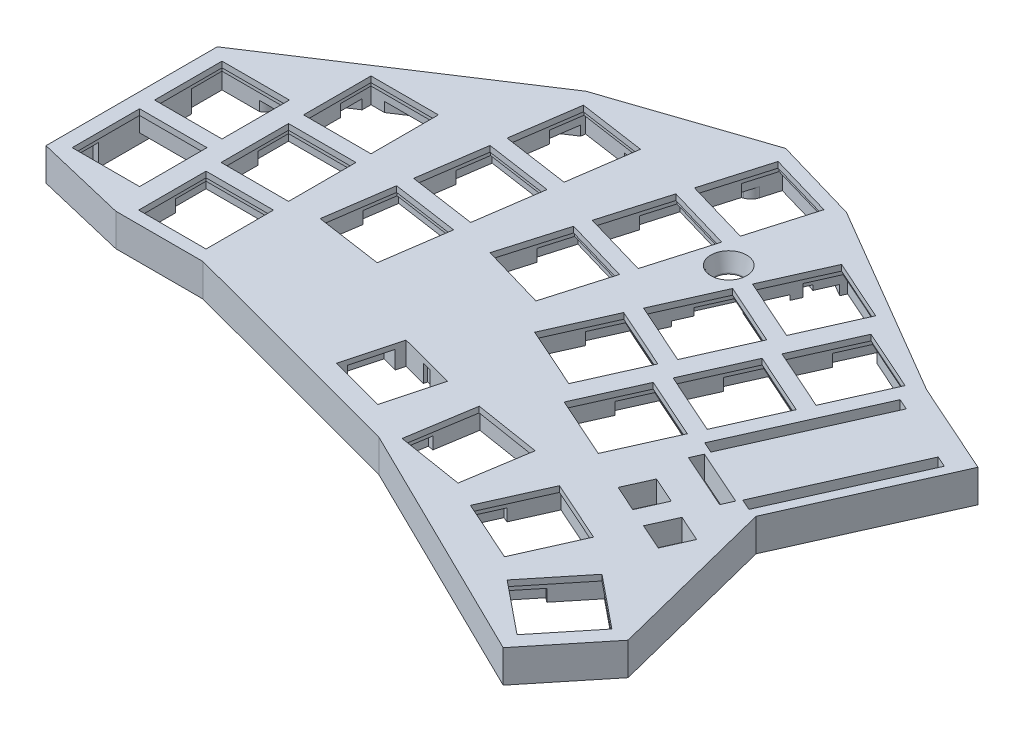
SolidWorks part; units mm, degrees
ref_plane "Front Plane" through (0, 0, 0) normal (0, 0, 1) x (1, 0, 0)
ref_plane "Top Plane" through (0, 0, 0) normal (0, 1, 0) x (1, 0, 0)
ref_plane "Right Plane" through (0, 0, 0) normal (1, 0, 0) x (0, 0, -1)
sketch "Ergogen Drawing" plane through (0, 0, 0) normal (0, 1, 0) x (1, 0, 0)
  line L0 (0.027, 17.9992) -> (18.027, 17.9992)
  line L1 (18.027, 17.9992) -> (18.027, -0.0008)
  line L2 (18.027, -0.0008) -> (0.027, -0.0008)
  line L3 (0.027, -0.0008) -> (0.027, 17.9992)
  line L4 (0.027, 34.9992) -> (18.027, 34.9992)
  line L5 (18.027, 34.9992) -> (18.027, 16.9992)
  line L6 (18.027, 16.9992) -> (0.027, 16.9992)
  line L7 (0.027, 16.9992) -> (0.027, 34.9992)
  line L8 (18.027, 15.9992) -> (36.027, 15.9992)
  line L9 (36.027, 15.9992) -> (36.027, -2.0008)
  line L10 (36.027, -2.0008) -> (18.027, -2.0008)
  line L11 (18.027, -2.0008) -> (18.027, 15.9992)
  line L12 (18.027, 32.9992) -> (36.027, 32.9992)
  line L13 (36.027, 32.9992) -> (36.027, 14.9992)
  line L14 (36.027, 14.9992) -> (18.027, 14.9992)
  line L15 (18.027, 14.9992) -> (18.027, 32.9992)
  line L16 (18.027, 49.9992) -> (36.027, 49.9992)
  line L17 (36.027, 49.9992) -> (36.027, 31.9992)
  line L18 (36.027, 31.9992) -> (18.027, 31.9992)
  line L19 (18.027, 31.9992) -> (18.027, 49.9992)
  line L20 (41.3768, 32.6051) -> (59.3329, 31.3495)
  line L21 (59.3329, 31.3495) -> (58.0773, 13.3933)
  line L22 (58.0773, 13.3933) -> (40.1211, 14.6489)
  line L23 (40.1211, 14.6489) -> (41.3768, 32.6051)
  line L24 (42.5626, 49.5637) -> (60.5188, 48.3081)
  line L25 (60.5188, 48.3081) -> (59.2631, 30.3519)
  line L26 (59.2631, 30.3519) -> (41.307, 31.6075)
  line L27 (41.307, 31.6075) -> (42.5626, 49.5637)
  line L28 (43.7485, 66.5223) -> (61.7046, 65.2667)
  line L29 (61.7046, 65.2667) -> (60.449, 47.3105)
  line L30 (60.449, 47.3105) -> (42.4929, 48.5661)
  line L31 (42.4929, 48.5661) -> (43.7485, 66.5223)
  line L32 (66.0898, 43.7082) -> (83.8507, 40.7838)
  line L33 (83.8507, 40.7838) -> (80.9263, 23.023)
  line L34 (80.9263, 23.023) -> (63.1655, 25.9473)
  line L35 (63.1655, 25.9473) -> (66.0898, 43.7082)
  line L36 (68.8517, 60.4823) -> (86.6126, 57.558)
  line L37 (86.6126, 57.558) -> (83.6882, 39.7971)
  line L38 (83.6882, 39.7971) -> (65.9274, 42.7215)
  line L39 (65.9274, 42.7215) -> (68.8517, 60.4823)
  line L40 (71.6136, 77.2565) -> (89.3745, 74.3321)
  line L41 (89.3745, 74.3321) -> (86.4501, 56.5713)
  line L42 (86.4501, 56.5713) -> (68.6893, 59.4956)
  line L43 (68.6893, 59.4956) -> (71.6136, 77.2565)
  line L44 (88.5581, 32.769) -> (105.9366, 28.0799)
  line L45 (105.9366, 28.0799) -> (101.2475, 10.7014)
  line L46 (101.2475, 10.7014) -> (83.869, 15.3905)
  line L47 (83.869, 15.3905) -> (88.5581, 32.769)
  line L48 (92.9866, 49.182) -> (110.3652, 44.4929)
  line L49 (110.3652, 44.4929) -> (105.6761, 27.1144)
  line L50 (105.6761, 27.1144) -> (88.2976, 31.8035)
  line L51 (88.2976, 31.8035) -> (92.9866, 49.182)
  line L52 (97.4152, 65.595) -> (114.7937, 60.906)
  line L53 (114.7937, 60.906) -> (110.1046, 43.5274)
  line L54 (110.1046, 43.5274) -> (92.7261, 48.2165)
  line L55 (92.7261, 48.2165) -> (97.4152, 65.595)
  line L56 (107.0448, 26.9674) -> (124.0477, 21.0597)
  line L57 (124.0477, 21.0597) -> (118.14, 4.0568)
  line L58 (118.14, 4.0568) -> (101.1371, 9.9645)
  line L59 (101.1371, 9.9645) -> (107.0448, 26.9674)
  line L60 (112.6243, 43.0257) -> (129.6273, 37.118)
  line L61 (129.6273, 37.118) -> (123.7195, 20.1151)
  line L62 (123.7195, 20.1151) -> (106.7166, 26.0228)
  line L63 (106.7166, 26.0228) -> (112.6243, 43.0257)
  line L64 (118.2039, 59.084) -> (135.2068, 53.1763)
  line L65 (135.2068, 53.1763) -> (129.299, 36.1734)
  line L66 (129.299, 36.1734) -> (112.2961, 42.0811)
  line L67 (112.2961, 42.0811) -> (118.2039, 59.084)
  line L68 (95.4197, 6.4051) -> (112.5714, 0.9445)
  line L69 (112.5714, 0.9445) -> (107.1108, -16.2072)
  line L70 (107.1108, -16.2072) -> (89.959, -10.7466)
  line L71 (89.959, -10.7466) -> (95.4197, 6.4051)
  line L72 (116.0129, -0.5249) -> (131.9353, -8.9198)
  line L73 (131.9353, -8.9198) -> (123.5404, -24.8423)
  line L74 (123.5404, -24.8423) -> (107.6179, -16.4473)
  line L75 (107.6179, -16.4473) -> (116.0129, -0.5249)
  line L76 (135.0644, -10.9721) -> (149.2602, -22.0392)
  line L77 (149.2602, -22.0392) -> (138.1931, -36.235)
  line L78 (138.1931, -36.235) -> (123.9973, -25.1679)
  line L79 (123.9973, -25.1679) -> (135.0644, -10.9721)
sketch "Layout Based on OG" plane through (0, 0, 0) normal (0, 1, 0) x (1, 0, 0)
  line L0 (0, 0) -> (0, 17) construction
  line L1 (0, 17) -> (18, 17) construction
  line L2 (18, 17) -> (18, 0) construction
  line L3 (18, 0) -> (0, 0) construction
  line L4 (2.05, 1.55) -> (2.05, 15.45)
  line L5 (2.05, 15.45) -> (15.95, 15.45)
  line L6 (15.95, 15.45) -> (15.95, 1.55)
  line L7 (15.95, 1.55) -> (2.05, 1.55)
  line L8 (109.1798, 58.6066) -> (27, -125.5436) construction
  line L9 (27, 46.7087) -> (27, -125.5436) construction
  line L10 (84.3863, 71.4039) -> (27, -125.5436) construction
  line L11 (54.2678, 62.3831) -> (27, -125.5436) construction
  line L12 (44.7261, 45.0233) -> (58.4821, 43.0274)
  line L13 (2.05, 18.55) -> (15.95, 18.55)
  line L14 (2.05, 18.55) -> (2.05, 32.45)
  line L15 (2.05, 32.45) -> (15.95, 32.45)
  line L16 (15.95, 18.55) -> (15.95, 32.45)
  line L17 (20.05, 31.2587) -> (33.95, 31.2587)
  line L18 (20.05, 31.2587) -> (20.05, 45.1587)
  line L19 (20.05, 45.1587) -> (33.95, 45.1587)
  line L20 (33.95, 31.2587) -> (33.95, 45.1587)
  line L21 (33.95, 28.1587) -> (20.05, 28.1587)
  line L22 (33.95, 28.1587) -> (33.95, 14.2587)
  line L23 (33.95, 14.2587) -> (20.05, 14.2587)
  line L24 (20.05, 28.1587) -> (20.05, 14.2587)
  line L25 (20.05, -2.7413) -> (33.95, -2.7413)
  line L26 (20.05, -2.7413) -> (20.05, 11.1587)
  line L27 (20.05, 11.1587) -> (33.95, 11.1587)
  line L28 (33.95, -2.7413) -> (33.95, 11.1587)
  line L29 (44.7261, 45.0233) -> (42.7302, 31.2674)
  line L30 (58.4821, 43.0274) -> (56.4861, 29.2714)
  line L31 (42.7302, 31.2674) -> (56.4861, 29.2714)
  line L32 (42.285, 28.1995) -> (56.041, 26.2036)
  line L33 (42.285, 28.1995) -> (40.2891, 14.4436)
  line L34 (56.041, 26.2036) -> (54.045, 12.4476)
  line L35 (40.2891, 14.4436) -> (54.045, 12.4476)
  line L36 (47.1672, 61.8472) -> (60.9232, 59.8512)
  line L37 (47.1672, 61.8472) -> (45.1712, 48.0912)
  line L38 (60.9232, 59.8512) -> (58.9272, 46.0953)
  line L39 (45.1712, 48.0912) -> (58.9272, 46.0953)
  line L40 (77.2802, 71.86) -> (90.6252, 67.9716)
  line L41 (77.2802, 71.86) -> (73.3917, 58.515)
  line L42 (90.6252, 67.9716) -> (86.7368, 54.6265)
  line L43 (73.3917, 58.515) -> (86.7368, 54.6265)
  line L44 (85.8695, 51.6503) -> (72.5245, 55.5388)
  line L45 (85.8695, 51.6503) -> (81.9811, 38.3053)
  line L46 (72.5245, 55.5388) -> (68.6361, 42.1937)
  line L47 (81.9811, 38.3053) -> (68.6361, 42.1937)
  line L48 (67.7688, 39.2175) -> (81.1139, 35.329)
  line L49 (67.7688, 39.2175) -> (63.8804, 25.8725)
  line L50 (81.1139, 35.329) -> (77.2254, 21.984)
  line L51 (63.8804, 25.8725) -> (77.2254, 21.984)
  line L52 (102.2015, 60.0235) -> (114.8949, 54.3589)
  line L53 (102.2015, 60.0235) -> (96.5369, 47.3301)
  line L54 (114.8949, 54.3589) -> (109.2302, 41.6655)
  line L55 (96.5369, 47.3301) -> (109.2302, 41.6655)
  line L56 (107.9669, 38.8346) -> (95.2735, 44.4992)
  line L57 (107.9669, 38.8346) -> (102.3023, 26.1412)
  line L58 (95.2735, 44.4992) -> (89.6089, 31.8058)
  line L59 (102.3023, 26.1412) -> (89.6089, 31.8058)
  line L60 (101.039, 23.3103) -> (88.3456, 28.9749)
  line L61 (101.039, 23.3103) -> (95.3744, 10.6169)
  line L62 (88.3456, 28.9749) -> (82.681, 16.2815)
  line L63 (95.3744, 10.6169) -> (82.681, 16.2815)
  line L64 (117.7053, 50.5958) -> (130.3987, 44.9312)
  line L65 (117.7053, 50.5958) -> (112.0407, 37.9024)
  line L66 (130.3987, 44.9312) -> (124.734, 32.2378)
  line L67 (112.0407, 37.9024) -> (124.734, 32.2378)
  line L68 (123.4707, 29.4069) -> (110.7773, 35.0715)
  line L69 (123.4707, 29.4069) -> (117.8061, 16.7135)
  line L70 (110.7773, 35.0715) -> (105.1127, 22.3782)
  line L71 (117.8061, 16.7135) -> (105.1127, 22.3782)
  line L72 (116.5428, 13.8826) -> (103.8494, 19.5473)
  line L73 (116.5428, 13.8826) -> (110.8782, 1.1892)
  line L74 (103.8494, 19.5473) -> (98.1848, 6.8539)
  line L75 (110.8782, 1.1892) -> (98.1848, 6.8539)
  line L76 (90.1692, -2.6429) -> (103.8962, -4.8292)
  line L77 (90.1692, -2.6429) -> (87.9829, -16.3699)
  line L78 (103.8962, -4.8292) -> (101.7099, -18.5562)
  line L79 (87.9829, -16.3699) -> (101.7099, -18.5562)
  line L80 (112.6329, -8.5638) -> (125.3263, -14.2284)
  line L81 (112.6329, -8.5638) -> (106.9683, -21.2572)
  line L82 (125.3263, -14.2284) -> (119.6617, -26.9218)
  line L83 (106.9683, -21.2572) -> (119.6617, -26.9218)
  line L84 (132.8305, -19.9983) -> (143.6253, -28.7552)
  line L85 (132.8305, -19.9983) -> (124.0737, -30.7931)
  line L86 (143.6253, -28.7552) -> (134.8684, -39.55)
  line L87 (124.0737, -30.7931) -> (134.8684, -39.55)
  line L88 (0, 0) -> (0, 34) construction
  line L89 (0, 34) -> (18, 46.7087) construction
  line L90 (18, 46.7087) -> (45.361, 63.6755) construction
  line L91 (45.361, 63.6755) -> (75.7456, 73.9216) construction
  line L92 (75.7456, 73.9216) -> (93.027, 68.8862) construction
  line L93 (93.027, 68.8862) -> (117.3986, 54.9389) construction
  line L94 (117.3986, 54.9389) -> (132.9024, 45.5112) construction
  line L95 (146.1938, -28.843) -> (135.484, -42.0452) construction
  line L96 (135.484, -42.0452) -> (85.7146, -17.5782) construction
  line L97 (0, 0) -> (18, -4.2913) construction
  line L98 (132.9024, 45.5112) -> (119.0465, 14.4627) construction
  line L99 (18, -4.2913) -> (36, -4.2913) construction
  line L100 (36, -4.2913) -> (85.7146, -17.5782) construction
  line L101 (119.0465, 14.4627) -> (137.3104, 6.3121) construction
  line L102 (137.3104, 6.3121) -> (151.1662, 37.3607) construction
  line L103 (151.1662, 37.3607) -> (132.9024, 45.5112) construction
  line L104 (146.1938, -28.843) -> (137.3104, 6.3121) construction
  line L105 (137.3104, 6.3121) -> (151.1662, 37.3607) construction
  line L106 (151.1662, 37.3607) -> (132.9024, 45.5112) construction
  line L107 (119.9597, 14.0551) -> (132.3892, 41.9075)
  line L108 (132.3892, 41.9075) -> (134.6722, 40.8887)
  line L109 (134.6722, 40.8887) -> (122.2427, 13.0363)
  line L110 (122.2427, 13.0363) -> (119.9597, 14.0551)
  line L111 (136.3972, 6.7197) -> (148.8267, 34.5721)
  line L112 (148.8267, 34.5721) -> (146.5437, 35.5909)
  line L113 (146.5437, 35.5909) -> (134.1142, 7.7385)
  line L114 (134.1142, 7.7385) -> (136.3972, 6.7197)
  line L115 (79.4058, -12.7868) -> (67.8127, -9.6883)
  line L116 (67.8127, -9.6883) -> (70.8336, 1.6149)
  line L117 (70.8336, 1.6149) -> (82.4267, -1.4835)
  line L118 (82.4267, -1.4835) -> (79.4058, -12.7868)
  line L119 (97.0327, -3.7361) -> (94.8464, -17.4631) construction
  line L120 (118.9913, -2.8379) -> (121.4364, 2.6412)
  line L121 (121.4364, 2.6412) -> (126.9156, 0.1961)
  line L122 (76.6302, 0.0657) -> (73.6092, -11.2375) construction
  line L123 (126.9156, 0.1961) -> (124.4704, -5.2831)
  line L124 (124.4704, -5.2831) -> (118.9913, -2.8379)
  line L125 (128.4611, -7.064) -> (130.9062, -1.5848)
  line L126 (130.9062, -1.5848) -> (136.3854, -4.03)
  line L127 (136.3854, -4.03) -> (133.9402, -9.5091)
  line L128 (133.9402, -9.5091) -> (128.4611, -7.064)
  line L137 (124.176, 1.4187) -> (121.7308, -4.0605) construction
  line L138 (133.6458, -2.8074) -> (131.2006, -8.2865) construction
  line L139 (126.7317, 7.1456) -> (128.1784, 10.3874) construction
  line L140 (135.0103, 42.8732) -> (147.795, 37.1678) construction
  line L141 (147.795, 37.1678) -> (133.1241, 4.2929) construction
  line L142 (133.1241, 4.2929) -> (120.3393, 9.9982) construction
  line L143 (120.3393, 9.9982) -> (135.0103, 42.8732) construction
  line L144 (120.9329, 9.7333) -> (121.9517, 12.0163)
  line L145 (121.9517, 12.0163) -> (133.5493, 6.8407)
  line L146 (133.5493, 6.8407) -> (132.5305, 4.5578)
  line L147 (132.5305, 4.5578) -> (120.9329, 9.7333)
  line L148 (126.9156, 0.1961) -> (140.3735, -5.8097) construction
  line L164 (-1, 34.5181) -> (-1, -0.7896)
  line L165 (-1, -0.7896) -> (17.8824, -5.2913)
  line L166 (17.8824, -5.2913) -> (35.8687, -5.2913)
  line L167 (35.8687, -5.2913) -> (85.3615, -18.5189)
  line L168 (85.3615, -18.5189) -> (135.7583, -43.2944)
  line L169 (135.7583, -43.2944) -> (147.2861, -29.0838)
  line L170 (147.2861, -29.0838) -> (138.3648, 6.2211)
  line L171 (138.3648, 6.2211) -> (152.487, 37.8664)
  line L172 (152.487, 37.8664) -> (133.3678, 46.3986)
  line L173 (133.3678, 46.3986) -> (117.9068, 55.8002) construction
  line L174 (117.9068, 55.8002) -> (93.4207, 69.8131) construction
  line L175 (93.4207, 69.8131) -> (75.7238, 74.9696)
  line L176 (75.7238, 74.9696) -> (44.9321, 64.5862)
  line L177 (44.9321, 64.5862) -> (17.4476, 47.5429) construction
  line L178 (17.4476, 47.5429) -> (-1, 34.5181) construction
  line L179 (-1, 34.5181) -> (44.9321, 64.5862)
  line L180 (133.3678, 46.3986) -> (93.4207, 69.8131)
  line L181 (27, -125.5436) -> (90.7493, 48.2155) construction
  circle A0 centre (142.6577, -23.0128) radius 2 construction
  circle A1 centre (142.6577, -23.0128) radius 1
  circle A2 centre (99.1237, -21.9416) radius 2 construction
  circle A3 centre (99.1237, -21.9416) radius 1
  circle A6 centre (16.2, -1.8061) radius 2 construction
  circle A7 centre (16.2, -1.8061) radius 1
  circle A8 centre (7.0467, 36.2) radius 2 construction
  circle A9 centre (7.0467, 36.2) radius 1
  circle A10 centre (72.7535, 70.802) radius 2 construction
  circle A11 centre (72.7535, 70.802) radius 1
  circle A12 centre (144.6437, 38.0814) radius 2 construction
  circle A13 centre (144.6437, 38.0814) radius 1
  circle A14 centre (90.7493, 48.2155) radius 3
  point P10 (110.8277, 18.1304)
  point P11 (117.7557, 33.6547)
  point P128 (75.1197, -5.5859)
  point P129 (95.9395, -10.5996)
  point P146 (127.7505, 9.4285)
  point P148 (128.1784, 10.3874)
  point P150 (122.9534, -1.3209)
  line B0 (18, 29.7087) -> (18, 46.7087) construction
  line B1 (18, 46.7087) -> (36, 46.7087) construction
  line B2 (36, 46.7087) -> (36, 29.7087) construction
  line B3 (36, 29.7087) -> (18, 29.7087) construction
  line B4 (20.05, 31.2587) -> (20.05, 45.1587) construction
  line B5 (20.05, 45.1587) -> (33.95, 45.1587) construction
  line B6 (33.95, 45.1587) -> (33.95, 31.2587) construction
  line B7 (33.95, 31.2587) -> (20.05, 31.2587) construction
  line B8 (18, 12.7087) -> (18, 29.7087) construction
  line B9 (18, 29.7087) -> (36, 29.7087) construction
  line B10 (36, 29.7087) -> (36, 12.7087) construction
  line B11 (36, 12.7087) -> (18, 12.7087) construction
  line B12 (20.05, 14.2587) -> (20.05, 28.1587) construction
  line B13 (20.05, 28.1587) -> (33.95, 28.1587) construction
  line B14 (33.95, 28.1587) -> (33.95, 14.2587) construction
  line B15 (33.95, 14.2587) -> (20.05, 14.2587) construction
  line B16 (18, -4.2913) -> (18, 12.7087) construction
  line B17 (18, 12.7087) -> (36, 12.7087) construction
  line B18 (36, 12.7087) -> (36, -4.2913) construction
  line B19 (36, -4.2913) -> (18, -4.2913) construction
  line B20 (20.05, -2.7413) -> (20.05, 11.1587) construction
  line B21 (20.05, 11.1587) -> (33.95, 11.1587) construction
  line B22 (33.95, 11.1587) -> (33.95, -2.7413) construction
  line B23 (33.95, -2.7413) -> (20.05, -2.7413) construction
  line B24 (42.9199, 46.8516) -> (45.361, 63.6755) construction
  line B25 (45.361, 63.6755) -> (63.1745, 61.0908) construction
  line B26 (63.1745, 61.0908) -> (60.7334, 44.267) construction
  line B27 (60.7334, 44.267) -> (42.9199, 46.8516) construction
  line B28 (45.1712, 48.0912) -> (47.1672, 61.8472) construction
  line B29 (47.1672, 61.8472) -> (60.9232, 59.8512) construction
  line B30 (60.9232, 59.8512) -> (58.9272, 46.0953) construction
  line B31 (58.9272, 46.0953) -> (45.1712, 48.0912) construction
  line B32 (40.4788, 30.0278) -> (42.9199, 46.8516) construction
  line B33 (42.9199, 46.8516) -> (60.7334, 44.267) construction
  line B34 (60.7334, 44.267) -> (58.2923, 27.4431) construction
  line B35 (58.2923, 27.4431) -> (40.4788, 30.0278) construction
  line B36 (42.7302, 31.2674) -> (44.7261, 45.0233) construction
  line B37 (44.7261, 45.0233) -> (58.4821, 43.0274) construction
  line B38 (58.4821, 43.0274) -> (56.4861, 29.2714) construction
  line B39 (56.4861, 29.2714) -> (42.7302, 31.2674) construction
  line B40 (38.0377, 13.204) -> (40.4788, 30.0278) construction
  line B41 (40.4788, 30.0278) -> (58.2923, 27.4431) construction
  line B42 (58.2923, 27.4431) -> (55.8512, 10.6193) construction
  line B43 (55.8512, 10.6193) -> (38.0377, 13.204) construction
  line B44 (40.2891, 14.4436) -> (42.285, 28.1995) construction
  line B45 (42.285, 28.1995) -> (56.041, 26.2036) construction
  line B46 (56.041, 26.2036) -> (54.045, 12.4476) construction
  line B47 (54.045, 12.4476) -> (40.2891, 14.4436) construction
  line B48 (70.99, 57.6004) -> (75.7456, 73.9216) construction
  line B49 (75.7456, 73.9216) -> (93.027, 68.8862) construction
  line B50 (93.027, 68.8862) -> (88.2713, 52.5649) construction
  line B51 (88.2713, 52.5649) -> (70.99, 57.6004) construction
  line B52 (73.3917, 58.515) -> (77.2802, 71.86) construction
  line B53 (77.2802, 71.86) -> (90.6252, 67.9716) construction
  line B54 (90.6252, 67.9716) -> (86.7368, 54.6265) construction
  line B55 (86.7368, 54.6265) -> (73.3917, 58.515) construction
  line B56 (66.2343, 41.2791) -> (70.99, 57.6004) construction
  line B57 (70.99, 57.6004) -> (88.2713, 52.5649) construction
  line B58 (88.2713, 52.5649) -> (83.5156, 36.2437) construction
  line B59 (83.5156, 36.2437) -> (66.2343, 41.2791) construction
  line B60 (68.6361, 42.1937) -> (72.5245, 55.5388) construction
  line B61 (72.5245, 55.5388) -> (85.8695, 51.6503) construction
  line B62 (85.8695, 51.6503) -> (81.9811, 38.3053) construction
  line B63 (81.9811, 38.3053) -> (68.6361, 42.1937) construction
  line B64 (61.4786, 24.9578) -> (66.2343, 41.2791) construction
  line B65 (66.2343, 41.2791) -> (83.5156, 36.2437) construction
  line B66 (83.5156, 36.2437) -> (78.76, 19.9224) construction
  line B67 (78.76, 19.9224) -> (61.4786, 24.9578) construction
  line B68 (63.8804, 25.8725) -> (67.7688, 39.2175) construction
  line B69 (67.7688, 39.2175) -> (81.1139, 35.329) construction
  line B70 (81.1139, 35.329) -> (77.2254, 21.984) construction
  line B71 (77.2254, 21.984) -> (63.8804, 25.8725) construction
  line B72 (80.1772, 15.7015) -> (87.1052, 31.2258) construction
  line B73 (87.1052, 31.2258) -> (103.5427, 23.8903) construction
  line B74 (103.5427, 23.8903) -> (96.6147, 8.366) construction
  line B75 (96.6147, 8.366) -> (80.1772, 15.7015) construction
  line B76 (82.681, 16.2815) -> (88.3456, 28.9749) construction
  line B77 (88.3456, 28.9749) -> (101.039, 23.3103) construction
  line B78 (101.039, 23.3103) -> (95.3744, 10.6169) construction
  line B79 (95.3744, 10.6169) -> (82.681, 16.2815) construction
  line B80 (87.1052, 31.2258) -> (94.0331, 46.7501) construction
  line B81 (94.0331, 46.7501) -> (110.4706, 39.4146) construction
  line B82 (110.4706, 39.4146) -> (103.5427, 23.8903) construction
  line B83 (103.5427, 23.8903) -> (87.1052, 31.2258) construction
  line B84 (89.6089, 31.8058) -> (95.2735, 44.4992) construction
  line B85 (95.2735, 44.4992) -> (107.9669, 38.8346) construction
  line B86 (107.9669, 38.8346) -> (102.3023, 26.1412) construction
  line B87 (102.3023, 26.1412) -> (89.6089, 31.8058) construction
  line B88 (94.0331, 46.7501) -> (100.9611, 62.2744) construction
  line B89 (100.9611, 62.2744) -> (117.3986, 54.9389) construction
  line B90 (117.3986, 54.9389) -> (110.4706, 39.4146) construction
  line B91 (110.4706, 39.4146) -> (94.0331, 46.7501) construction
  line B92 (96.5369, 47.3301) -> (102.2015, 60.0235) construction
  line B93 (102.2015, 60.0235) -> (114.8949, 54.3589) construction
  line B94 (114.8949, 54.3589) -> (109.2302, 41.6655) construction
  line B95 (109.2302, 41.6655) -> (96.5369, 47.3301) construction
  line B96 (109.5369, 37.3224) -> (116.4649, 52.8467) construction
  line B97 (116.4649, 52.8467) -> (132.9024, 45.5112) construction
  line B98 (132.9024, 45.5112) -> (125.9744, 29.9869) construction
  line B99 (125.9744, 29.9869) -> (109.5369, 37.3224) construction
  line B100 (112.0407, 37.9024) -> (117.7053, 50.5958) construction
  line B101 (117.7053, 50.5958) -> (130.3987, 44.9312) construction
  line B102 (130.3987, 44.9312) -> (124.734, 32.2378) construction
  line B103 (124.734, 32.2378) -> (112.0407, 37.9024) construction
  line B104 (102.609, 21.7981) -> (109.5369, 37.3224) construction
  line B105 (109.5369, 37.3224) -> (125.9744, 29.9869) construction
  line B106 (125.9744, 29.9869) -> (119.0465, 14.4627) construction
  line B107 (119.0465, 14.4627) -> (102.609, 21.7981) construction
  line B108 (105.1127, 22.3782) -> (110.7773, 35.0715) construction
  line B109 (110.7773, 35.0715) -> (123.4707, 29.4069) construction
  line B110 (123.4707, 29.4069) -> (117.8061, 16.7135) construction
  line B111 (117.8061, 16.7135) -> (105.1127, 22.3782) construction
  line B112 (95.6811, 6.2738) -> (102.609, 21.7981) construction
  line B113 (102.609, 21.7981) -> (119.0465, 14.4627) construction
  line B114 (119.0465, 14.4627) -> (112.1185, -1.0616) construction
  line B115 (112.1185, -1.0616) -> (95.6811, 6.2738) construction
  line B116 (98.1848, 6.8539) -> (103.8494, 19.5473) construction
  line B117 (103.8494, 19.5473) -> (116.5428, 13.8826) construction
  line B118 (116.5428, 13.8826) -> (110.8782, 1.1892) construction
  line B119 (110.8782, 1.1892) -> (98.1848, 6.8539) construction
  line B120 (104.4646, -21.8372) -> (111.3925, -6.3129) construction
  line B121 (111.3925, -6.3129) -> (127.83, -13.6484) construction
  line B122 (127.83, -13.6484) -> (120.9021, -29.1727) construction
  line B123 (120.9021, -29.1727) -> (104.4646, -21.8372) construction
  line B124 (106.9683, -21.2572) -> (112.6329, -8.5638) construction
  line B125 (112.6329, -8.5638) -> (125.3263, -14.2284) construction
  line B126 (125.3263, -14.2284) -> (119.6617, -26.9218) construction
  line B127 (119.6617, -26.9218) -> (106.9683, -21.2572) construction
  line B128 (85.7146, -17.5782) -> (88.3885, -0.7898) construction
  line B129 (88.3885, -0.7898) -> (106.1645, -3.621) construction
  line B130 (106.1645, -3.621) -> (103.4906, -20.4094) construction
  line B131 (103.4906, -20.4094) -> (85.7146, -17.5782) construction
  line B132 (87.9829, -16.3699) -> (90.1692, -2.6429) construction
  line B133 (90.1692, -2.6429) -> (103.8962, -4.8292) construction
  line B134 (103.8962, -4.8292) -> (101.7099, -18.5562) construction
  line B135 (101.7099, -18.5562) -> (87.9829, -16.3699) construction
  line B136 (121.5051, -30.7054) -> (132.215, -17.5031) construction
  line B137 (132.215, -17.5031) -> (146.1938, -28.843) construction
  line B138 (146.1938, -28.843) -> (135.484, -42.0452) construction
  line B139 (135.484, -42.0452) -> (121.5051, -30.7054) construction
  line B140 (124.0737, -30.7931) -> (132.8305, -19.9983) construction
  line B141 (132.8305, -19.9983) -> (143.6253, -28.7552) construction
  line B142 (143.6253, -28.7552) -> (134.8684, -39.55) construction
  line B143 (134.8684, -39.55) -> (124.0737, -30.7931) construction
  line B144 (0, 17) -> (0, 34) construction
  line B145 (0, 34) -> (18, 34) construction
  line B146 (18, 34) -> (18, 17) construction
  line B147 (18, 17) -> (0, 17) construction
  line B148 (2.05, 18.55) -> (2.05, 32.45) construction
  line B149 (2.05, 32.45) -> (15.95, 32.45) construction
  line B150 (15.95, 32.45) -> (15.95, 18.55) construction
  line B151 (15.95, 18.55) -> (2.05, 18.55) construction
  dimension "D46" = 4
  dimension "D47" = 2
  dimension "D48" = 3
  dimension "D52" = 4
  dimension "D53" = 2
  dimension "D54" = 4
  dimension "D55" = 2
  dimension "D57" = 4
  dimension "D58" = 2
  dimension "D60" = 4
  dimension "D61" = 2
  dimension "D63" = 4
  dimension "D64" = 2
  dimension "D51" = 3.85
  dimension "D83" = 6
  dimension "D85" = 3.75
  dimension "D1" = 18
  dimension "D2" = 17
  dimension "D3" = 13.9
  dimension "D4" = 13.9
  dimension "D5" = 2.05
  dimension "D6" = 1.55
  dimension "D7" = 205.1378
  dimension "D8" = 201.6553
  dimension "D9" = 189.8947
  dimension "D10" = 8.256
  dimension "D11" = 15
  dimension "D12" = 15
  dimension "D13" = 1.4278
  dimension "D14" = 0.974
  dimension "D15" = 1.5327
  dimension "D16" = 0.6031
  dimension "D17" = 5.9541
  dimension "D18" = 2.5593
  dimension "D19" = 7.805
  dimension "D20" = 7.989
  dimension "D21" = 172.2524
  dimension "D22" = 2.2911
  dimension "D23" = 4.2913
  dimension "D24" = 34
  dimension "D25" = 20
  dimension "D26" = 30.5
  dimension "D27" = 2.5
  dimension "D28" = 1
  dimension "D29" = 2.5
  dimension "D30" = 30.5
  dimension "D31" = 18
  dimension "D32" = 11.7
  dimension "D33" = 12
  dimension "D34" = 3
  dimension "D35" = 21.415
  dimension "D36" = 6
  dimension "D37" = 6
  dimension "D38" = 6
  dimension "D39" = 6
  dimension "D40" = 14
  dimension "D41" = 36
  dimension "D42" = 12.7
  dimension "D43" = 2.5
  dimension "D44" = 9.27
  dimension "D45" = 4.37
  dimension "D49" = 3.85
  dimension "D50" = 3
  dimension "D56" = 3
  dimension "D59" = 3
  dimension "D62" = 3
  dimension "D65" = 3
  dimension "D66" = 3.75
  dimension "D67" = 1
  dimension "D68" = 1
  dimension "D69" = 1
  dimension "D70" = 1
  dimension "D71" = 1
  dimension "D72" = 1
  dimension "D73" = 1
  dimension "D74" = 1
  dimension "D75" = 1
  dimension "D76" = 1
  dimension "D77" = 1
  dimension "D78" = 1
  dimension "D79" = 1
  dimension "D80" = 1
  dimension "D81" = 1
  dimension "D82" = 3.902
  dimension "D84" = 2.75
sketch_block_instance "Block-ChocSwitchCutout-3"
sketch_block "Block-ChocSwitchCutout" parameters "D1"=18, "D2"=17, "D3"=13.9, "D4"=13.9, "D5"=2.05, "D6"=1.55
sketch_block_instance "Block-ChocSwitchCutout-4"
sketch_block_instance "Block-ChocSwitchCutout-5"
sketch_block_instance "Block-ChocSwitchCutout-6"
sketch_block_instance "Block-ChocSwitchCutout-7"
sketch_block_instance "Block-ChocSwitchCutout-8"
sketch_block_instance "Block-ChocSwitchCutout-9"
sketch_block_instance "Block-ChocSwitchCutout-10"
sketch_block_instance "Block-ChocSwitchCutout-11"
sketch_block_instance "Block-ChocSwitchCutout-20"
sketch_block_instance "Block-ChocSwitchCutout-23"
sketch_block_instance "Block-ChocSwitchCutout-24"
sketch_block_instance "Block-ChocSwitchCutout-27"
sketch_block_instance "Block-ChocSwitchCutout-28"
sketch_block_instance "Block-ChocSwitchCutout-29"
sketch_block_instance "Block-ChocSwitchCutout-32"
sketch_block_instance "Block-ChocSwitchCutout-33"
sketch_block_instance "Block-ChocSwitchCutout-34"
sketch_block_instance "Block-ChocSwitchCutout-37"
other "AlignGroup1"
extrude "Top Plate" add sketch "Layout Based on OG" along normal blind 1.2 contours L105 L106 L94 L93 L92 L91 L90 L89 L88 L97 L99 L100 L96 L95 L104 L73 L75 L74 L72 L69 L71 L70 L68 L61 L63 L62 L60 L57 L59 L58 L56 L45 L47 L46 L44 L6 L7 L4 L5 L16 L13 L14 L15 | A9 | A7 | A3 | A1 | A13 | A11 region at (81.1817, 0, -18.7955) region at (142.6577, 0, 23.0128) region at (99.1237, 0, 21.9416) region at (16.2, 0, 1.8061) region at (7.0467, 0, -36.2) region at (72.7535, 0, -70.802) region at (144.6437, 0, -38.0814)
sketch "Sketch1" plane through (0, 0, 0) normal (0, -1, 0) x (1, 0, 0)
  line L0 (124.9363, -31.7095) -> (130.927, -45.1335)
  line L1 (130.927, -45.1335) -> (117.503, -51.1241)
  line L2 (117.503, -51.1241) -> (111.5124, -37.7002)
  line L3 (111.5124, -37.7002) -> (124.9363, -31.7095)
  line L4 (118.0084, -16.1852) -> (123.999, -29.6092)
  line L5 (117.7053, -50.5958) -> (130.3987, -44.9312) construction
  line L6 (123.999, -29.6092) -> (110.5751, -35.5998)
  line L7 (117.7053, -50.5958) -> (112.0407, -37.9024) construction
  line L8 (110.5751, -35.5998) -> (104.5844, -22.1759)
  line L9 (104.5844, -22.1759) -> (118.0084, -16.1852)
  line L10 (123.4707, -29.4069) -> (117.8061, -16.7135) construction
  line L11 (111.0804, -0.661) -> (117.0711, -14.0849)
  line L12 (117.8061, -16.7135) -> (105.1127, -22.3782) construction
  line L13 (117.0711, -14.0849) -> (103.6471, -20.0755)
  line L14 (103.6471, -20.0755) -> (97.6565, -6.6516)
  line L15 (97.6565, -6.6516) -> (111.0804, -0.661)
  line L16 (103.8494, -19.5473) -> (98.1848, -6.8539) construction
  line L17 (110.8782, -1.1892) -> (98.1848, -6.8539) construction
  line L18 (95.5766, -10.0886) -> (101.5673, -23.5126)
  line L19 (101.5673, -23.5126) -> (88.1433, -29.5032)
  line L20 (88.1433, -29.5032) -> (82.1527, -16.0793)
  line L21 (82.1527, -16.0793) -> (95.5766, -10.0886)
  line L22 (101.039, -23.3103) -> (88.3456, -28.9749) construction
  line L23 (101.039, -23.3103) -> (95.3744, -10.6169) construction
  line L24 (102.5046, -25.6129) -> (108.4952, -39.0369)
  line L25 (108.4952, -39.0369) -> (95.0713, -45.0275)
  line L26 (95.0713, -45.0275) -> (89.0806, -31.6036)
  line L27 (89.0806, -31.6036) -> (102.5046, -25.6129)
  line L28 (102.3023, -26.1412) -> (89.6089, -31.8058) construction
  line L29 (95.2735, -44.4992) -> (89.6089, -31.8058) construction
  line L30 (109.4325, -41.1372) -> (115.4231, -54.5612)
  line L31 (115.4231, -54.5612) -> (101.9992, -60.5518)
  line L32 (101.9992, -60.5518) -> (96.0086, -47.1279)
  line L33 (96.0086, -47.1279) -> (109.4325, -41.1372)
  line L34 (102.2015, -60.0235) -> (114.8949, -54.3589) construction
  line L35 (114.8949, -54.3589) -> (109.2302, -41.6655) construction
  line L36 (119.864, 27.4501) -> (125.8546, 14.0261)
  line L37 (125.8546, 14.0261) -> (112.4307, 8.0355)
  line L38 (112.4307, 8.0355) -> (106.44, 21.4594)
  line L39 (106.44, 21.4594) -> (119.864, 27.4501)
  line L40 (125.3263, 14.2284) -> (119.6617, 26.9218) construction
  line L41 (106.9683, 21.2572) -> (119.6617, 26.9218) construction
  line L42 (144.1879, 28.6966) -> (134.9271, 40.1126)
  line L43 (134.9271, 40.1126) -> (123.511, 30.8517)
  line L44 (123.511, 30.8517) -> (132.7719, 19.4357)
  line L45 (132.7719, 19.4357) -> (144.1879, 28.6966)
  line L46 (143.6253, 28.7552) -> (134.8684, 39.55) construction
  line L47 (132.8305, 19.9983) -> (143.6253, 28.7552) construction
  line L48 (132.8305, 19.9983) -> (124.0737, 30.7931) construction
  line L49 (104.3541, 4.4971) -> (102.042, 19.0142)
  line L50 (102.042, 19.0142) -> (87.5249, 16.702)
  line L51 (87.5249, 16.702) -> (89.8371, 2.185)
  line L52 (89.8371, 2.185) -> (104.3541, 4.4971)
  line L61 (86.3655, -51.9224) -> (82.2532, -37.8093)
  line L62 (103.8962, 4.8292) -> (101.7099, 18.5562) construction
  line L63 (82.2532, -37.8093) -> (68.1401, -41.9216)
  line L64 (87.9829, 16.3699) -> (101.7099, 18.5562) construction
  line L65 (91.1211, -68.2437) -> (87.0089, -54.1306)
  line L66 (87.0089, -54.1306) -> (72.8958, -58.2429)
  line L67 (72.8958, -58.2429) -> (77.008, -72.3559)
  line L68 (77.008, -72.3559) -> (91.1211, -68.2437)
  line L69 (61.3764, -60.1896) -> (59.2656, -45.642)
  line L70 (59.2656, -45.642) -> (44.718, -47.7528)
  line L71 (44.718, -47.7528) -> (46.8288, -62.3005)
  line L72 (46.8288, -62.3005) -> (61.3764, -60.1896)
  line L73 (34.35, -45.5587) -> (34.35, -30.8587)
  line L74 (34.35, -30.8587) -> (19.65, -30.8587)
  line L75 (19.65, -30.8587) -> (19.65, -45.5587)
  line L76 (19.65, -45.5587) -> (34.35, -45.5587)
  line L77 (90.6252, -67.9716) -> (86.7368, -54.6265) construction
  line L78 (47.1672, -61.8472) -> (45.1712, -48.0912) construction
  line L79 (33.95, -31.2587) -> (33.95, -45.1587) construction
  line L80 (73.3917, -58.515) -> (86.7368, -54.6265) construction
  line L81 (60.9232, -59.8512) -> (58.9272, -46.0953) construction
  line L82 (45.1712, -48.0912) -> (58.9272, -46.0953) construction
  line L83 (68.1401, -41.9216) -> (72.2524, -56.0347)
  line L84 (20.05, -31.2587) -> (33.95, -31.2587) construction
  line L85 (72.2524, -56.0347) -> (86.3655, -51.9224)
  line L86 (85.8695, -51.6503) -> (81.9811, -38.3053) construction
  line L87 (81.9811, -38.3053) -> (68.6361, -42.1937) construction
  line L88 (81.6098, -35.6012) -> (77.4976, -21.4881)
  line L89 (77.4976, -21.4881) -> (63.3845, -25.6003)
  line L90 (63.3845, -25.6003) -> (67.4967, -39.7134)
  line L91 (67.4967, -39.7134) -> (81.6098, -35.6012)
  line L92 (81.1139, -35.329) -> (77.2254, -21.984) construction
  line L93 (63.8804, -25.8725) -> (77.2254, -21.984) construction
  line L94 (58.9353, -43.3658) -> (56.8245, -28.8181)
  line L95 (56.8245, -28.8181) -> (42.2769, -30.929)
  line L96 (42.2769, -30.929) -> (44.3877, -45.4766)
  line L97 (44.3877, -45.4766) -> (58.9353, -43.3658)
  line L98 (58.4821, -43.0274) -> (56.4861, -29.2714) construction
  line L99 (42.7302, -31.2674) -> (56.4861, -29.2714) construction
  line L100 (56.4943, -26.542) -> (54.3834, -11.9943)
  line L101 (54.3834, -11.9943) -> (39.8358, -14.1052)
  line L102 (39.8358, -14.1052) -> (41.9466, -28.6528)
  line L103 (41.9466, -28.6528) -> (56.4943, -26.542)
  line L104 (56.041, -26.2036) -> (54.045, -12.4476) construction
  line L105 (40.2891, -14.4436) -> (54.045, -12.4476) construction
  line L106 (34.35, -28.5587) -> (34.35, -13.8587)
  line L107 (34.35, -13.8587) -> (19.65, -13.8587)
  line L108 (19.65, -13.8587) -> (19.65, -28.5587)
  line L109 (19.65, -28.5587) -> (34.35, -28.5587)
  line L110 (33.95, -28.1587) -> (33.95, -14.2587) construction
  line L111 (33.95, -14.2587) -> (20.05, -14.2587) construction
  line L112 (34.35, -11.5587) -> (34.35, 3.1413)
  line L113 (34.35, 3.1413) -> (19.65, 3.1413)
  line L114 (19.65, 3.1413) -> (19.65, -11.5587)
  line L115 (19.65, -11.5587) -> (34.35, -11.5587)
  line L116 (20.05, 2.7413) -> (33.95, 2.7413) construction
  line L117 (20.05, 2.7413) -> (20.05, -11.1587) construction
  line L118 (16.35, -15.85) -> (16.35, -1.15)
  line L119 (16.35, -1.15) -> (1.65, -1.15)
  line L120 (1.65, -1.15) -> (1.65, -15.85)
  line L121 (1.65, -15.85) -> (16.35, -15.85)
  line L122 (2.05, -1.55) -> (2.05, -15.45) construction
  line L123 (15.95, -1.55) -> (2.05, -1.55) construction
  line L124 (16.35, -32.85) -> (16.35, -18.15)
  line L125 (16.35, -18.15) -> (1.65, -18.15)
  line L126 (1.65, -18.15) -> (1.65, -32.85)
  line L127 (1.65, -32.85) -> (16.35, -32.85)
  line L128 (2.05, -18.55) -> (2.05, -32.45) construction
  line L129 (2.05, -18.55) -> (15.95, -18.55) construction
  dimension "D1" = 14.7
  dimension "D2" = 14.7
  dimension "D3" = 0.4
  dimension "D4" = 0.4
  dimension "D5" = 14.7
  dimension "D6" = 14.7
  dimension "D7" = 0.4
  dimension "D8" = 0.4
  dimension "D9" = 14.7
  dimension "D10" = 14.7
  dimension "D11" = 0.4
  dimension "D12" = 0.4
  dimension "D13" = 14.7
  dimension "D14" = 14.7
  dimension "D15" = 0.4
  dimension "D16" = 0.4
  dimension "D17" = 14.7
  dimension "D18" = 14.7
  dimension "D19" = 0.4
  dimension "D20" = 0.4
  dimension "D21" = 14.7
  dimension "D22" = 0.4
  dimension "D23" = 0.4
  dimension "D24" = 14.7
  dimension "D25" = 14.7
  dimension "D26" = 14.7
  dimension "D27" = 0.4
  dimension "D28" = 0.4
  dimension "D29" = 14.7
  dimension "D30" = 14.7
  dimension "D31" = 0.4
  dimension "D32" = 0.4
  dimension "D33" = 14.7
  dimension "D34" = 14.7
  dimension "D35" = 0.4
  dimension "D36" = 0.4
  dimension "D37" = 0.4
  dimension "D38" = 0.4
  dimension "D39" = 14.7
  dimension "D40" = 14.7
  dimension "D41" = 0.4
  dimension "D42" = 0.4
  dimension "D43" = 14.7
  dimension "D44" = 14.7
  dimension "D45" = 14.7
  dimension "D46" = 0.4
  dimension "D47" = 0.4
  dimension "D48" = 14.7
  dimension "D49" = 14.7
  dimension "D50" = 14.7
  dimension "D51" = 0.4
  dimension "D52" = 0.4
  dimension "D53" = 14.7
  dimension "D54" = 14.7
  dimension "D55" = 0.4
  dimension "D56" = 0.4
  dimension "D57" = 14.7
  dimension "D58" = 14.7
  dimension "D59" = 0.4
  dimension "D60" = 0.4
  dimension "D61" = 14.7
  dimension "D62" = 14.7
  dimension "D63" = 0.4
  dimension "D64" = 0.4
  dimension "D65" = 14.7
  dimension "D66" = 14.7
  dimension "D67" = 0.4
  dimension "D68" = 0.4
  dimension "D69" = 14.7
  dimension "D70" = 14.7
  dimension "D71" = 0.4
  dimension "D72" = 0.4
  dimension "D73" = 14.7
  dimension "D74" = 14.7
  dimension "D75" = 0.4
  dimension "D76" = 0.4
  dimension "D77" = 14.7
  dimension "D78" = 14.7
  dimension "D79" = 0.4
  dimension "D80" = 0.4
extrude "Boss-Extrude2" add sketch "Layout Based on OG<7>" against normal blind 5.5 contours L172 L180 L175 L176 L179 L164 L165 L166 L167 L168 L169 L170 L171 A13 A11 A9 A7 A3 A1 L146 L147 L144 L145 L127 L128 L125 L126 L123 L124 L120 L121 L117 L118 L115 L116 L109 L110 L107 L108 region at (81.1817, 0, -18.7955)
sketch "Layout Based on OG<7>" plane through (0, 0, 0) normal (0, 1, 0) x (1, 0, 0) same geometry as "Layout Based on OG"
extrude "Cut-Extrude1" cut sketch "Sketch1" along normal blind 5.5
sketch "Sketch4" plane through (0, -5.5, 0) normal (0, -1, 0) x (1, 0, 0)
  line L0 (74.3817, 12.2203) -> (77.7899, -0.5321)
  line L1 (77.7899, -0.5321) -> (75.8577, -1.0485)
  line L2 (75.8577, -1.0485) -> (72.4495, 11.7039)
  line L3 (72.4495, 11.7039) -> (74.3817, 12.2203)
  line L4 (67.8127, 9.6883) -> (70.8336, -1.6149) construction
  line L6 (79.4058, 12.7868) -> (67.8127, 9.6883) construction
  line L8 (82.4267, 1.4835) -> (79.4058, 12.7868) construction
  line L9 (83.0232, 11.8386) -> (85.0888, 4.1099)
  line L10 (85.0888, 4.1099) -> (76.394, 1.7861)
  line L11 (76.394, 1.7861) -> (67.2162, -0.6668)
  line L12 (67.2162, -0.6668) -> (65.1505, 7.0619)
  line L14 (83.0232, 11.8386) -> (74.3284, 9.5148)
  line L15 (74.3284, 9.5148) -> (65.1505, 7.0619)
  dimension "D1" = 2
  dimension "D2" = 13.2
  dimension "D3" = 0.75
  dimension "D4" = 5
  dimension "D5" = 9
  dimension "D6" = 9.5
  dimension "D7" = 3.25
  dimension "D8" = 8
  dimension "D9" = 1.85
  dimension "D10" = 9
extrude "Cut-Extrude2" cut sketch "Sketch4" against normal blind 5.7 contours L9 L14 L0 L10 | L2 L15 L12 L11 | L10 L11 L2 L1 L0 | L15 L14 L0 L3 L2 region at (73.7512, -5.5, 10.7062) region at (80.0709, -5.5, 6.9092) region at (76.4882, -5.5, 0.4656) region at (70.1685, -5.5, 4.2626)
sketch "Sketch5" plane through (0, -5.5, 0) normal (0, -1, 0) x (1, 0, 0)
  line L0 (90.4768, -61.9215) -> (92.5469, -69.0261)
  line L1 (92.5469, -69.0261) -> (76.2257, -73.7817)
  line L2 (76.2257, -73.7817) -> (74.1556, -66.6772)
  line L3 (74.1556, -66.6772) -> (90.4768, -61.9215)
  line L4 (91.1211, -68.2437) -> (87.0089, -54.1306) construction
  line L5 (80.9655, -29.279) -> (83.0356, -36.3835)
  line L6 (83.0356, -36.3835) -> (66.7143, -41.1392)
  line L7 (66.7143, -41.1392) -> (64.6442, -34.0347)
  line L8 (64.6442, -34.0347) -> (80.9655, -29.279)
  line L9 (72.2524, -56.0347) -> (86.3655, -51.9224) construction
  line L10 (77.008, -72.3559) -> (91.1211, -68.2437) construction
  line L11 (85.7211, -45.6003) -> (87.7913, -52.7048)
  line L12 (87.7913, -52.7048) -> (71.47, -57.4605)
  line L13 (71.47, -57.4605) -> (69.3999, -50.3559)
  line L14 (69.3999, -50.3559) -> (85.7211, -45.6003)
  line L15 (68.1401, -41.9216) -> (72.2524, -56.0347) construction
  line L16 (81.6098, -35.6012) -> (77.4976, -21.4881) construction
  line L17 (67.4967, -39.7134) -> (81.6098, -35.6012) construction
  line L18 (113.9263, -48.385) -> (116.942, -55.1427)
  line L19 (116.942, -55.1427) -> (101.4177, -62.0706)
  line L20 (101.4177, -62.0706) -> (98.402, -55.313)
  line L21 (98.402, -55.313) -> (113.9263, -48.385)
  line L22 (96.0086, -47.1279) -> (101.9992, -60.5518) construction
  line L23 (106.9983, -32.8608) -> (110.014, -39.6184)
  line L24 (110.014, -39.6184) -> (94.4897, -46.5463)
  line L25 (94.4897, -46.5463) -> (91.474, -39.7887)
  line L26 (91.474, -39.7887) -> (106.9983, -32.8608)
  line L27 (100.0704, -17.3365) -> (103.0861, -24.0941)
  line L28 (103.0861, -24.0941) -> (87.5618, -31.022)
  line L29 (87.5618, -31.022) -> (84.5461, -24.2644)
  line L30 (84.5461, -24.2644) -> (100.0704, -17.3365)
  line L31 (115.5742, -7.9088) -> (118.5899, -14.6664)
  line L32 (118.5899, -14.6664) -> (103.0656, -21.5944)
  line L33 (103.0656, -21.5944) -> (100.0499, -14.8367)
  line L34 (100.0499, -14.8367) -> (115.5742, -7.9088)
  line L35 (122.5021, -23.4331) -> (125.5178, -30.1907)
  line L36 (125.5178, -30.1907) -> (109.9935, -37.1187)
  line L37 (109.9935, -37.1187) -> (106.9778, -30.361)
  line L38 (106.9778, -30.361) -> (122.5021, -23.4331)
  line L39 (129.4301, -38.9574) -> (132.4458, -45.715)
  line L40 (132.4458, -45.715) -> (116.9215, -52.6429)
  line L41 (116.9215, -52.6429) -> (113.9058, -45.8853)
  line L42 (113.9058, -45.8853) -> (129.4301, -38.9574)
  line L43 (130.927, -45.1335) -> (124.9363, -31.7095) construction
  line L44 (117.503, -51.1241) -> (130.927, -45.1335) construction
  line L45 (115.4231, -54.5612) -> (109.4325, -41.1372) construction
  line L46 (101.9992, -60.5518) -> (115.4231, -54.5612) construction
  line L47 (89.0806, -31.6036) -> (95.0713, -45.0275) construction
  line L48 (95.0713, -45.0275) -> (108.4952, -39.0369) construction
  line L49 (88.1433, -29.5032) -> (101.5673, -23.5126) construction
  line L50 (101.5673, -23.5126) -> (95.5766, -10.0886) construction
  line L51 (117.0711, -14.0849) -> (111.0804, -0.661) construction
  line L52 (103.6471, -20.0755) -> (117.0711, -14.0849) construction
  line L53 (123.999, -29.6092) -> (118.0084, -16.1852) construction
  line L54 (110.5751, -35.5998) -> (123.999, -29.6092) construction
  line L55 (61.6171, -53.8393) -> (62.6797, -61.1626)
  line L56 (62.6797, -61.1626) -> (45.8558, -63.6037)
  line L57 (45.8558, -63.6037) -> (44.7932, -56.2804)
  line L58 (44.7932, -56.2804) -> (61.6171, -53.8393)
  line L59 (61.3764, -60.1896) -> (59.2656, -45.642) construction
  line L60 (59.176, -37.0154) -> (60.2386, -44.3387)
  line L61 (60.2386, -44.3387) -> (43.4147, -46.7798)
  line L62 (43.4147, -46.7798) -> (42.3521, -39.4565)
  line L63 (42.3521, -39.4565) -> (59.176, -37.0154)
  line L64 (56.7349, -20.1916) -> (57.7975, -27.5149)
  line L65 (57.7975, -27.5149) -> (40.9736, -29.956)
  line L66 (40.9736, -29.956) -> (39.911, -22.6327)
  line L67 (39.911, -22.6327) -> (56.7349, -20.1916)
  line L68 (35.5, -39.3087) -> (35.5, -46.7087)
  line L69 (35.5, -46.7087) -> (18.5, -46.7087)
  line L70 (18.5, -46.7087) -> (18.5, -39.3087)
  line L71 (18.5, -39.3087) -> (35.5, -39.3087)
  line L72 (34.35, -45.5587) -> (34.35, -30.8587) construction
  line L73 (35.5, -22.3087) -> (35.5, -29.7087)
  line L74 (35.5, -29.7087) -> (18.5, -29.7087)
  line L75 (18.5, -29.7087) -> (18.5, -22.3087)
  line L76 (18.5, -22.3087) -> (35.5, -22.3087)
  line L77 (17.5, -26.6) -> (17.5, -34)
  line L78 (17.5, -34) -> (0.5, -34)
  line L79 (0.5, -34) -> (0.5, -26.6)
  line L80 (0.5, -26.6) -> (17.5, -26.6)
  line L81 (17.5, 0) -> (17.5, -7.4)
  line L82 (17.5, -7.4) -> (0.5, -7.4)
  line L83 (0.5, -7.4) -> (0.5, 0)
  line L84 (0.5, 0) -> (17.5, 0)
  line L85 (35.5, -5.3087) -> (35.5, -12.7087)
  line L86 (35.5, -12.7087) -> (18.5, -12.7087)
  line L87 (18.5, -12.7087) -> (18.5, -5.3087)
  line L88 (18.5, -5.3087) -> (35.5, -5.3087)
  line L89 (46.8288, -62.3005) -> (61.3764, -60.1896) construction
  line L90 (58.9353, -43.3658) -> (56.8245, -28.8181) construction
  line L91 (44.3877, -45.4766) -> (58.9353, -43.3658) construction
  line L92 (41.9466, -28.6528) -> (56.4943, -26.542) construction
  line L93 (39.8358, -14.1052) -> (41.9466, -28.6528) construction
  line L94 (19.65, -45.5587) -> (34.35, -45.5587) construction
  line L95 (19.65, -30.8587) -> (19.65, -45.5587) construction
  line L96 (19.65, -28.5587) -> (34.35, -28.5587) construction
  line L97 (34.35, -28.5587) -> (34.35, -13.8587) construction
  line L98 (19.65, -11.5587) -> (34.35, -11.5587) construction
  line L99 (19.65, 3.1413) -> (19.65, -11.5587) construction
  line L101 (1.65, -1.15) -> (1.65, -15.85) construction
  line L102 (1.65, -32.85) -> (16.35, -32.85) construction
  line L103 (1.65, -18.15) -> (1.65, -32.85) construction
  line L104 (120.4455, 28.9689) -> (123.4612, 22.2113)
  line L105 (123.4612, 22.2113) -> (107.9369, 15.2833)
  line L106 (107.9369, 15.2833) -> (104.9212, 22.0409)
  line L107 (104.9212, 22.0409) -> (120.4455, 28.9689)
  line L108 (102.9968, 20.3307) -> (104.1607, 13.0228)
  line L109 (104.1607, 13.0228) -> (87.3723, 10.3489)
  line L110 (87.3723, 10.3489) -> (86.2084, 17.6568)
  line L111 (86.2084, 17.6568) -> (102.9968, 20.3307)
  line L112 (135.0957, 41.7302) -> (139.7576, 35.9834)
  line L113 (139.7576, 35.9834) -> (126.5554, 25.2735)
  line L114 (126.5554, 25.2735) -> (121.8934, 31.0203)
  line L115 (121.8934, 31.0203) -> (135.0957, 41.7302)
  line L116 (87.5249, 16.702) -> (89.8371, 2.185) construction
  line L117 (123.511, 30.8517) -> (132.7719, 19.4357) construction
  line L118 (106.44, 21.4594) -> (112.4307, 8.0355) construction
  line L119 (102.042, 19.0142) -> (87.5249, 16.702) construction
  line L120 (119.864, 27.4501) -> (106.44, 21.4594) construction
  line L121 (134.9271, 40.1126) -> (123.511, 30.8517) construction
  line L122 (16.35, -1.15) -> (1.65, -1.15) construction
  point P156 (106.429, 18.6621)
  dimension "D1" = 17
  dimension "D2" = 7.4
  dimension "D3" = 1.15
  dimension "D4" = 1.15
  dimension "D5" = 17
  dimension "D6" = 7.4
  dimension "D7" = 17
  dimension "D8" = 7.4
  dimension "D9" = 1.15
  dimension "D10" = 1.15
  dimension "D11" = 1.15
  dimension "D12" = 1.15
  dimension "D13" = 17
  dimension "D14" = 7.4
  dimension "D15" = 17
  dimension "D16" = 7.4
  dimension "D17" = 17
  dimension "D18" = 7.4
  dimension "D19" = 17
  dimension "D20" = 7.4
  dimension "D21" = 17
  dimension "D22" = 7.4
  dimension "D23" = 17
  dimension "D24" = 7.4
  dimension "D25" = 1.15
  dimension "D26" = 1.15
  dimension "D27" = 1.15
  dimension "D28" = 1.15
  dimension "D29" = 1.15
  dimension "D30" = 1.15
  dimension "D31" = 1.15
  dimension "D32" = 1.15
  dimension "D33" = 1.15
  dimension "D34" = 1.15
  dimension "D35" = 1.15
  dimension "D36" = 1.15
  dimension "D37" = 17
  dimension "D38" = 7.4
  dimension "D39" = 17
  dimension "D40" = 7.4
  dimension "D41" = 17
  dimension "D42" = 7.4
  dimension "D43" = 17
  dimension "D44" = 7.4
  dimension "D45" = 17
  dimension "D46" = 7.4
  dimension "D47" = 17
  dimension "D48" = 7.4
  dimension "D49" = 17
  dimension "D50" = 7.4
  dimension "D51" = 17
  dimension "D52" = 7.4
  dimension "D53" = 1.15
  dimension "D54" = 1.15
  dimension "D55" = 1.15
  dimension "D56" = 1.15
  dimension "D57" = 1.15
  dimension "D58" = 1.15
  dimension "D59" = 1.15
  dimension "D60" = 1.15
  dimension "D61" = 1.15
  dimension "D62" = 1.15
  dimension "D63" = 1.15
  dimension "D64" = 1.15
  dimension "D65" = 1.15
  dimension "D66" = 1.15
  dimension "D67" = 1.15
  dimension "D68" = 1.15
  dimension "D69" = 17
  dimension "D70" = 7.4
  dimension "D71" = 17
  dimension "D72" = 7.4
  dimension "D73" = 17
  dimension "D74" = 7.4
  dimension "D75" = 1.15
  dimension "D76" = 1.15
  dimension "D77" = 1.15
  dimension "D78" = 1.15
  dimension "D79" = 1.15
  dimension "D80" = 1.15
extrude "Cut-Extrude3" cut sketch "Sketch5" against normal blind 4.5
sketch "Sketch6" plane through (0, -5.5, 0) normal (0, -1, 0) x (1, 0, 0)
  line L0 (137.2986, 4.4375) -> (129.993, 1.1773)
  line L1 (129.993, 1.1773) -> (127.5479, 6.6564)
  line L2 (127.5479, 6.6564) -> (134.8534, 9.9166)
  line L3 (134.8534, 9.9166) -> (137.2986, 4.4375)
  line L4 (125.3836, 5.6906) -> (127.8288, 0.2114)
  line L5 (127.8288, 0.2114) -> (120.5232, -3.0488)
  line L6 (120.5232, -3.0488) -> (118.0781, 2.4304)
  line L7 (118.0781, 2.4304) -> (125.3836, 5.6906)
  line L8 (130.9062, 1.5848) -> (136.3854, 4.03) construction
  line L9 (121.4364, -2.6412) -> (126.9156, -0.1961) construction
  line L10 (133.9402, 9.5091) -> (128.4611, 7.064) construction
  line L11 (124.4704, 5.2831) -> (118.9913, 2.8379) construction
  point P10 (133.6458, 2.8074)
  point P11 (133.6458, 2.8074)
  point P14 (124.176, -1.4187)
  point P15 (124.176, -1.4187)
  dimension "D1" = 8
  dimension "D2" = 8
extrude "Cut-Extrude4" cut sketch "Sketch6" against normal blind 2.2
sketch "Sketch8" plane through (0, -5.5, 0) normal (0, -1, 0) x (1, 0, 0)
  line L0 (139.2044, 23.1731) -> (142.6548, 18.9197)
  line L1 (148.8267, -34.5721) -> (136.2559, -6.4032)
  line L2 (136.2559, -6.4032) -> (142.6548, 18.9197)
  line L3 (148.8267, -34.5721) -> (146.5437, -35.5909)
  line L4 (141.5212, -37.8323) -> (131.0194, -42.5188)
  line L5 (132.4458, -45.715) -> (129.4301, -38.9574) construction
  line L6 (100.9102, -60.9335) -> (116.4345, -54.0056)
  line L7 (1.65, -32.85) -> (1.65, -34)
  line L8 (116.942, -55.1427) -> (113.9263, -48.385) construction
  line L9 (0, -34) -> (18, -34) construction
  line L10 (116.4345, -54.0056) -> (116.9215, -52.6429)
  line L11 (98.402, -55.313) -> (101.4177, -62.0706) construction
  line L12 (100.9102, -60.9335) -> (91.7529, -66.301)
  line L13 (92.5469, -69.0261) -> (90.4768, -61.9215) construction
  line L14 (91.7529, -66.301) -> (75.4316, -71.0566)
  line L15 (74.1556, -66.6772) -> (76.2257, -73.7817) construction
  line L16 (75.4316, -71.0566) -> (75.1536, -70.1026)
  line L17 (73.5523, -68.433) -> (55.2073, -62.2468)
  line L18 (45.361, -63.6755) -> (63.1745, -61.0908) construction
  line L19 (55.2073, -62.2468) -> (45.7271, -62.7161)
  line L20 (44.7932, -56.2804) -> (45.8558, -63.6037) construction
  line L21 (45.7271, -62.7161) -> (21.2741, -46.7087)
  line L22 (18, -46.7087) -> (36, -46.7087) construction
  line L23 (21.2741, -46.7087) -> (18.5, -44.8928)
  line L24 (18.5, -39.3087) -> (18.5, -46.7087) construction
  line L25 (18.5, -44.8928) -> (8.4161, -38.2916)
  line L26 (138.4799, 24.0661) -> (131.9975, 39.2169)
  line L27 (133.3678, -46.3986) -> (93.4207, -69.8131) construction
  line L28 (113.9058, -45.8853) -> (116.9215, -52.6429) construction
  line L29 (116.9215, -52.6429) -> (131.0194, -42.5188)
  line L30 (100.9611, -62.2744) -> (117.3986, -54.9389) construction
  line L31 (1.65, -32.85) -> (1.65, -0.6347)
  line L32 (135.7583, 43.2944) -> (147.2861, 29.0838) construction
  line L33 (136.3972, -6.7197) -> (148.8267, -34.5721) construction
  line L34 (147.2861, 29.0838) -> (138.3648, -6.2211) construction
  line L35 (91.1211, -68.2437) -> (77.008, -72.3559) construction
  line L36 (75.7238, -74.9696) -> (44.9321, -64.5862) construction
  line L37 (-1, -34.5181) -> (44.9321, -64.5862) construction
  line L38 (1.65, -0.6347) -> (19.65, -0.6347)
  line L39 (19.65, 3.1413) -> (19.65, -11.5587) construction
  line L40 (131.9975, 39.2169) -> (100.7388, 23.8499)
  line L41 (129.6887, 11.6745) -> (123.8717, 9.0785) construction
  line L42 (35.5701, 3.1413) -> (86.3584, 16.7151)
  line L43 (86.2084, 17.6568) -> (87.3723, 10.3489) construction
  line L44 (-1, 0.7896) -> (17.8824, 5.2913) construction
  line L45 (130.5038, 9.8481) -> (124.6867, 7.2522)
  line L46 (35.8687, 5.2913) -> (85.3615, 18.5189) construction
  line L47 (34.35, 3.1413) -> (35.5701, 3.1413)
  line L48 (34.35, 3.1413) -> (19.65, 3.1413) construction
  line L49 (135.484, 42.0452) -> (121.5051, 30.7054) construction
  line L50 (85.3615, 18.5189) -> (135.7583, 43.2944) construction
  line L51 (1.65, -34) -> (8.2342, -34)
  line L52 (139.2044, 23.1731) -> (138.4799, 24.0661)
  line L53 (132.7719, 19.4357) -> (144.1879, 28.6966) construction
  line L54 (86.3584, 16.7151) -> (100.6424, 19.9557)
  line L55 (103.4906, 20.4094) -> (85.7146, 17.5782) construction
  line L56 (128.8737, 13.5009) -> (123.0566, 10.9049)
  line L63 (86.1692, -6.3146) -> (62.3834, -12.6717) construction
  line L64 (86.8147, -8.7299) -> (63.0289, -15.0869)
  line L65 (85.5237, -3.8994) -> (61.7379, -10.2565)
  line L66 (66.4366, -56.1669) -> (64.0032, -44.9546) construction
  line L67 (64.9707, -56.485) -> (62.5373, -45.2727)
  line L68 (67.9025, -55.8488) -> (65.4691, -44.6364)
  line L69 (39.9198, -53.3451) -> (39.4405, -46.7087) construction
  line L70 (38.4237, -53.4532) -> (37.9444, -46.8168)
  line L71 (41.4159, -53.2371) -> (40.9366, -46.6007)
  line L75 (133.9402, 9.5091) -> (128.4611, 7.064) construction
  line L76 (126.7317, -7.1456) -> (128.1784, -10.3874) construction
  line L77 (133.6458, 2.8074) -> (131.2006, 8.2865) construction
  line L78 (127.8288, 0.2114) -> (125.3836, 5.6906) construction
  line L79 (112.4307, 8.0355) -> (125.8546, 14.0261) construction
  line L85 (68.1401, -41.9216) -> (70.504, -50.0342) construction
  line L87 (44.718, -47.7528) -> (45.9313, -56.1152) construction
  line L88 (121.9517, -12.0163) -> (133.5493, -6.8407) construction
  line L91 (72.2524, -56.0347) -> (86.3655, -51.9224) construction
  line L92 (34.35, 3.1413) -> (19.65, -0.6347)
  line L93 (59.2656, -45.642) -> (44.718, -47.7528) construction
  circle A0 centre (136.6619, -29.3973) radius 2.5
  arc A1 (8.4161, -38.2916) -> (8.2342, -34) centre (7.0467, -36.2) ccw
  arc A2 (75.1536, -70.1026) -> (73.5523, -68.433) centre (72.7535, -70.802) ccw
  arc A3 (146.5437, -35.5909) -> (141.5212, -37.8323) centre (144.6437, -38.0814) ccw
  arc A5 (100.6424, 19.9557) -> (100.7388, 23.8499) centre (99.1237, 21.9416) ccw
  circle A6 centre (131.6966, -18.271) radius 2.5
  circle A8 centre (109.5914, 3.3881) radius 3.4349 construction
  arc A9 (130.5038, 9.8481) -> (128.8737, 13.5009) centre (129.6887, 11.6745) ccw
  arc A10 (123.0566, 10.9049) -> (124.6867, 7.2522) centre (123.8717, 9.0785) ccw
  arc A15 (86.8147, -8.7299) -> (85.5237, -3.8994) centre (86.1692, -6.3146) ccw
  arc A16 (61.7379, -10.2565) -> (63.0289, -15.0869) centre (62.3834, -12.6717) ccw
  arc A17 (64.9707, -56.485) -> (67.9025, -55.8488) centre (66.4366, -56.1669) ccw
  arc A18 (65.4691, -44.6364) -> (62.5373, -45.2727) centre (64.0032, -44.9546) ccw
  arc A19 (38.4237, -53.4532) -> (41.4159, -53.2371) centre (39.9198, -53.3451) ccw
  arc A20 (40.9366, -46.6007) -> (37.9444, -46.8168) centre (39.4405, -46.7087) ccw
  circle A23 centre (109.5914, 3.3881) radius 2.25
  point P109 (126.7802, 10.3765)
  point P128 (74.2763, -9.4932)
  point P135 (65.2199, -50.5607)
  point P142 (39.6801, -50.0269)
  dimension "D7" = 5
  dimension "D8" = 5
  dimension "D9" = 4.5
  dimension "D10" = 5
  dimension "D11" = 5
  dimension "D12" = 5
  dimension "D13" = 2.5
  dimension "D15" = 2
  dimension "D21" = 1.5
  dimension "D22" = 1.5
  dimension "D27" = 4
  dimension "D1" = 2
  dimension "D2" = 2
  dimension "D3" = 2
  dimension "D4" = 2
  dimension "D5" = 2
  dimension "D6" = 2
  dimension "D17" = 4
  dimension "D18" = 4.125
  dimension "D23" = 3.75
  dimension "D26" = 8
  dimension "D28" = 7.75
  dimension "D29" = 3.71
  dimension "D30" = 9.683
  dimension "D31" = 9.683
extrude "Cut-Extrude5" cut sketch "Sketch8" against normal blind 2
fillet "Fillet1" radius 1.5 19 edges at (38.184, -3.5, -50.135) (40.0278, -3.5, -54.8412) (41.1763, -3.5, -49.9189) (39.3324, -3.5, -45.2126) (63.685, -3.5, -43.4887) (66.6858, -3.5, -50.2426) (63.754, -3.5, -50.8789) (66.7547, -3.5, -57.6328) (74.9218, -3.5, -11.9084) (88.5844, -3.5, -5.6691) (59.9682, -3.5, -13.3172) (73.6308, -3.5, -7.0779) (127.5953, -3.5, 8.5501) (131.5151, -3.5, 12.4895) (125.9652, -3.5, 12.2029) (122.0453, -3.5, 8.2635) (109.5914, -3.5, 1.1381) (136.6619, -3.5, -31.8973) (131.6966, -3.5, -20.771)
sketch "Sketch9" plane through (0, -3.5, 0) normal (0, -1, 0) x (1, 0, 0)
  line L0 (92.2726, -35.6734) -> (81.4763, -39.6344)
  line L1 (81.4763, -39.6344) -> (89.2261, -60.7577)
  line L2 (89.2261, -60.7577) -> (100.0224, -56.7967)
  line L3 (100.0224, -56.7967) -> (92.2726, -35.6734)
  line L4 (27, 125.5436) -> (90.7493, -48.2155) construction
  line L5 (96.1475, -46.235) -> (85.3512, -50.196) construction
  point P6 (86.8745, -37.6539)
  point P9 (90.7493, -48.2155)
  dimension "D1" = 22.5
  dimension "D2" = 11.5
extrude "Cut-Extrude6" cut sketch "Sketch9" against normal blind 1
chamfer "Chamfer1" distance 0.7 distance2 3.5 1 edges at (90.7493, 1.2, -45.2155) first distance on face at (90.7493, 1.2, -45.2155)
sketch "Sketch11" plane through (0, -3.5, 0) normal (0, -1, 0) x (1, 0, 0)
  line L0 (61.6545, 10.1127) -> (66.044, -6.3109)
  line L1 (66.044, -6.3109) -> (39.9595, -13.2823)
  line L2 (39.9595, -13.2823) -> (35.5701, 3.1413)
  line L3 (35.5701, 3.1413) -> (61.6545, 10.1127)
  line L4 (86.3584, 16.7151) -> (35.5701, 3.1413) construction
  dimension "D1" = 17
  dimension "D2" = 27
extrude "Cut-Extrude7" cut sketch "Sketch11" against normal blind 4
sketch "Sketch12" plane through (0, 1.2, 0) normal (0, 1, 0) x (1, 0, 0)
  circle A0 centre (90.7493, 48.2155) radius 3.7
extrude "Boss-Extrude3" [suppressed] add sketch "Sketch12" against normal up to surface (3.7 mm away) separate body
